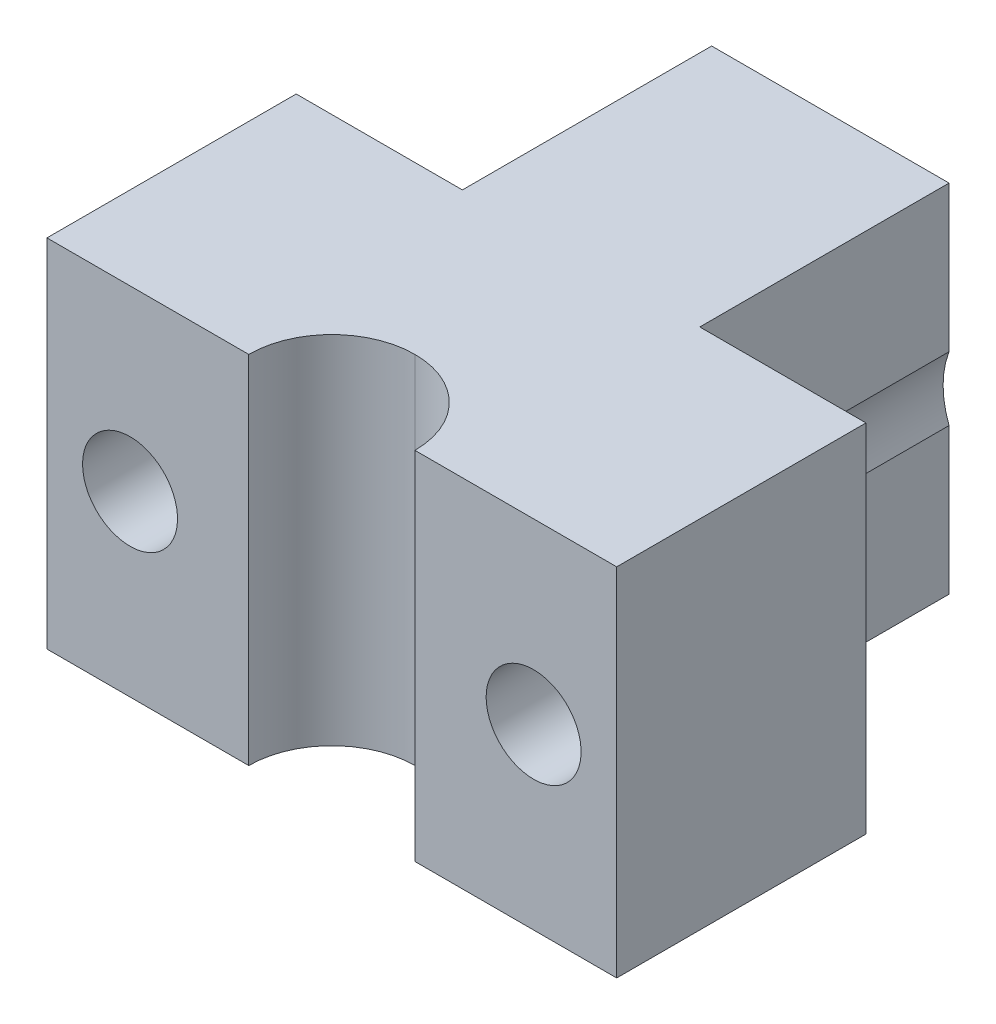
SolidWorks part; units mm, degrees
ref_plane "Спереди" through (0, 0, 0) normal (0, 0, 1) x (1, 0, 0)
ref_plane "Сверху" through (0, 0, 0) normal (0, 1, 0) x (1, 0, 0)
ref_plane "Справа" through (0, 0, 0) normal (1, 0, 0) x (0, 0, -1)
sketch "Эскиз1" plane through (0, 0, 0) normal (0, 1, 0) x (1, 0, 0)
  line L1 (-24, -10) -> (24, -10)
  line L2 (-24, -10) -> (-24, 10)
  line L3 (-24, 10) -> (24, 10)
  line L4 (24, -10) -> (24, 10)
  line L5 (-24, -10) -> (24, 10) construction
  line L6 (-24, 10) -> (24, -10) construction
  point P0 (0, 0)
  dimension "D1" = 48
  dimension "D2" = 20
extrude "Бобышка-Вытянуть1" add sketch "Эскиз1" along normal blind 30
sketch "Эскиз2" plane through (0, 0, 10) normal (0, 0, 1) x (1, 0, 0)
  line L0 (-7, 30) -> (-7, 0)
  line L1 (-24, 30) -> (24, 30) construction
  line L2 (-24, 0) -> (24, 0) construction
  line L3 (-7, 0) -> (7, 0)
  line L4 (7, 0) -> (7, 30)
  line L5 (7, 30) -> (-7, 30)
  dimension "D1" = 17
  dimension "D2" = 14
extrude "Вырез-Вытянуть1" cut sketch "Эскиз2" against normal blind 7
sketch "Эскиз7" plane through (24, 0, 0) normal (1, 0, 0) x (0, 0, -1)
  line L1 (32, 30) -> (32, 0)
  line L2 (32, 0) -> (10, 0)
  line L3 (-10, 0) -> (10, 0)
  line L4 (10, 0) -> (10.066, 0.2736)
  line L5 (10, 30) -> (32, 30)
  line L8 (10, 0) -> (10, 30)
  dimension "D3" = 22
extrude "Бобышка-Вытянуть2" add sketch "Эскиз7" against normal blind 48
sketch "Эскиз8" plane through (24, 0, 0) normal (1, 0, 0) x (0, 0, -1)
  line L0 (11, 0) -> (11, 30)
  line L1 (-10, 30) -> (32, 30) construction
  line L2 (11, 30) -> (32, 30)
  line L3 (11, 0) -> (32, 0)
  line L4 (32, 0) -> (32, 30)
  line L5 (-10, 0) -> (32, 0) construction
  point P16 (11, 0)
extrude "Вырез-Вытянуть2" cut sketch "Эскиз8" against normal blind 14
sketch "Эскиз9" plane through (-24, 0, 0) normal (-1, 0, 0) x (0, 0, 1)
  line L0 (-11, 0) -> (-11, 30)
  line L1 (-32, 30) -> (10, 30) construction
  line L2 (-11, 30) -> (-32, 30)
  line L3 (-32, 0) -> (10, 0) construction
  line L4 (-11, 0) -> (-32, 0)
  line L5 (-32, 0) -> (-32, 30)
  point P15 (-11, 0)
extrude "Вырез-Вытянуть3" cut sketch "Эскиз9" against normal blind 14
sketch "Эскиз11" plane through (-10, 0, 0) normal (-1, 0, 0) x (0, 0, 1)
  line L0 (-32, 30) -> (-11, 0) construction
  line L2 (-32, 0) -> (-11, 0) construction
  line L3 (-16.3, 4.8) -> (-16.3, 25.2)
  line L6 (-16.3, 4.8) -> (-26.7, 4.8)
  line L7 (-16.3, 25.2) -> (-26.7, 25.2)
  line L8 (-26.7, 4.8) -> (-26.7, 25.2)
  line L9 (-16.3, 4.8) -> (-26.7, 25.2) construction
  line L10 (-16.3, 25.2) -> (-26.7, 4.8) construction
  point P7 (-21.5, 15)
  point P8 (-21.5, 15)
  dimension "D1" = 20.4
  dimension "D2" = 10.4
extrude "Вырез-Вытянуть4" cut sketch "Эскиз11" against normal through all
sketch "Эскиз13" plane through (0, 0, -11) normal (0, 0, -1) x (-1, 0, 0)
  line L0 (24, 15) -> (10, 15) construction
  line L1 (24, 0) -> (24, 30) construction
  line L2 (10, 0) -> (10, 30) construction
  circle A0 centre (17, 15) radius 4
extrude "Вырез-Вытянуть5" cut sketch "Эскиз13" against normal through all
sketch "Эскиз14" plane through (0, 0, -11) normal (0, 0, -1) x (-1, 0, 0)
  line L0 (-24, 15) -> (-10, 15) construction
  line L1 (-24, 30) -> (-24, 0) construction
  line L2 (-10, 30) -> (-10, 0) construction
  circle A0 centre (-17, 15) radius 4
extrude "Вырез-Вытянуть6" cut sketch "Эскиз14" against normal through all
fillet "Скругление1" radius 7 2 edges at (-7, 15, 3) (7, 15, 3)
sketch "Sketch1" plane through (10, 0, 0) normal (1, 0, 0) x (0, 0, -1)
  line L0 (16.3, 25.2) -> (26.7, 4.8) construction
  line L2 (26.7, 4.8) -> (16.3, 4.8)
  line L3 (26.7, 4.8) -> (26.7, 25.2)
  line L4 (26.7, 25.2) -> (16.3, 25.2)
  line L5 (16.3, 4.8) -> (16.3, 25.2)
  line L6 (26.7, 4.8) -> (16.3, 25.2) construction
  line L7 (26.7, 25.2) -> (16.3, 4.8) construction
  point P4 (21.5, 15)
extrude "Boss-Extrude1" add sketch "Sketch1" against normal blind 4
sketch "Эскиз20" plane through (0, 0, -11) normal (0, 0, -1) x (-1, 0, 0)
  circle A0 centre (-17, 15) radius 7.5
  circle A1 centre (17, 15) radius 7.5
  dimension "D1" = 15
extrude "Вырез-Вытянуть8" cut sketch "Эскиз20" along normal through all
